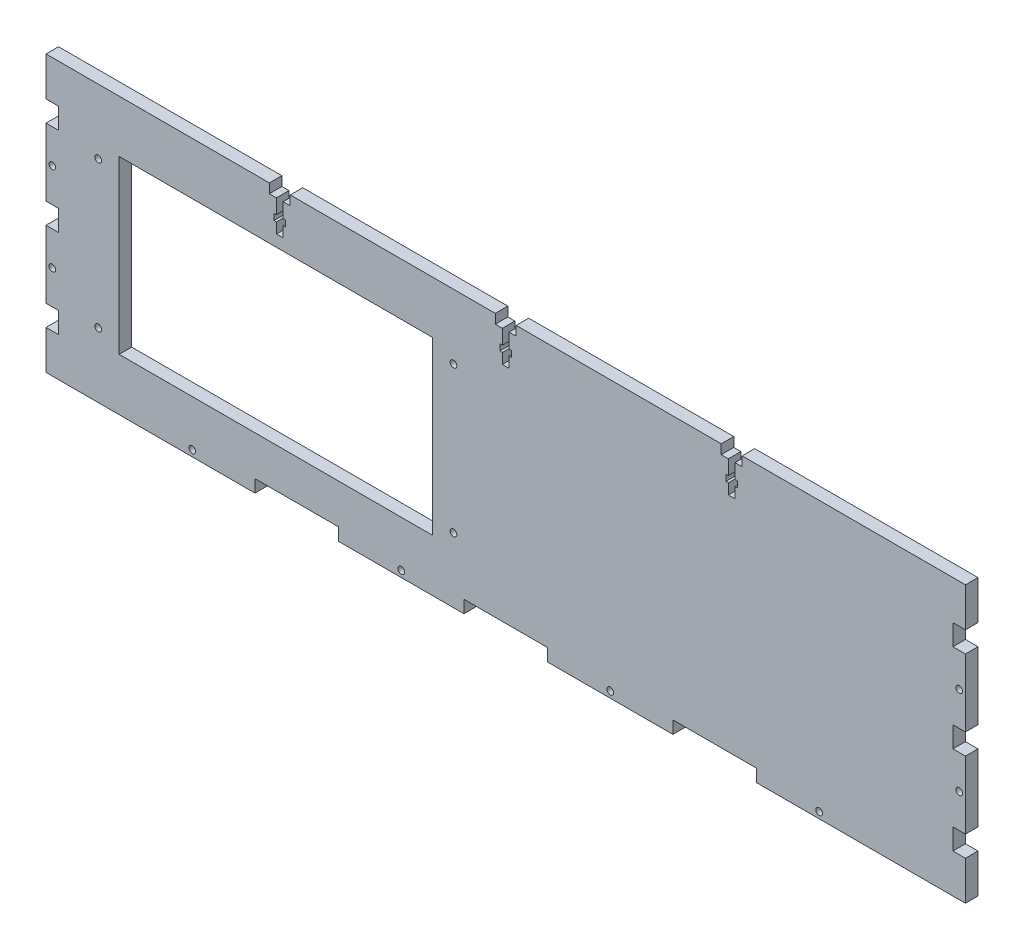
SolidWorks part; units mm, degrees
ref_plane "Front Plane" through (0, 0, 0) normal (0, 0, 1) x (1, 0, 0)
ref_plane "Top Plane" through (0, 0, 0) normal (0, 1, 0) x (1, 0, 0)
ref_plane "Right Plane" through (0, 0, 0) normal (1, 0, 0) x (0, 0, -1)
sketch "Sketch1" plane through (0, 0, 0) normal (0, 0, 1) x (1, 0, 0)
  line L1 (-220, -66) -> (220, -66)
  line L2 (-220, -66) -> (-220, 66)
  line L3 (-220, 66) -> (220, 66)
  line L4 (220, -66) -> (220, 66)
  line L5 (-220, -66) -> (220, 66) construction
  line L6 (-220, 66) -> (220, -66) construction
  point P0 (0, 0)
  dimension "D1" = 440
  dimension "D2" = 132
extrude "Boss-Extrude1" add sketch "Sketch1" along normal blind 6
sketch "Sketch2" plane through (0, 0, 0) normal (0, 0, -1) x (-1, 0, 0)
  line L0 (220, 47.3321) -> (220, 37.3321) construction
  line L1 (220, 37.3321) -> (214, 37.3321) construction
  line L2 (214, 37.3321) -> (214, 47.3321) construction
  line L3 (214, 47.3321) -> (220, 47.3321) construction
  line L12 (220, -37.3321) -> (220, -47.3321) construction
  line L13 (220, -47.3321) -> (214, -47.3321) construction
  line L14 (214, -47.3321) -> (214, -37.3321) construction
  line L15 (214, -37.3321) -> (220, -37.3321) construction
  line L16 (220, 47.3321) -> (220, 37.3321)
  line L17 (220, 37.3321) -> (214, 37.3321)
  line L18 (214, 37.3321) -> (214, 47.3321)
  line L19 (214, 47.3321) -> (220, 47.3321)
  line L20 (220, -37.3321) -> (220, -47.3321)
  line L21 (220, -47.3321) -> (214, -47.3321)
  line L22 (214, -47.3321) -> (214, -37.3321)
  line L23 (214, -37.3321) -> (220, -37.3321)
  line L24 (-214, -37.3321) -> (-214, -47.3321) construction
  line L25 (-214, -47.3321) -> (-220, -47.3321) construction
  line L26 (-220, -47.3321) -> (-220, -37.3321) construction
  line L27 (-220, -37.3321) -> (-214, -37.3321) construction
  line L28 (-214, 47.3321) -> (-214, 37.3321) construction
  line L29 (-214, 37.3321) -> (-220, 37.3321) construction
  line L30 (-220, 37.3321) -> (-220, 47.3321) construction
  line L31 (-220, 47.3321) -> (-214, 47.3321) construction
  line L32 (-214, -37.3321) -> (-214, -47.3321)
  line L33 (-214, -47.3321) -> (-220, -47.3321)
  line L34 (-220, -47.3321) -> (-220, -37.3321)
  line L35 (-220, -37.3321) -> (-214, -37.3321)
  line L36 (-214, 47.3321) -> (-214, 37.3321)
  line L37 (-214, 37.3321) -> (-220, 37.3321)
  line L38 (-220, 37.3321) -> (-220, 47.3321)
  line L39 (-220, 47.3321) -> (-214, 47.3321)
  line L44 (220, -5) -> (220, 5)
  line L45 (214, -5) -> (220, -5)
  line L46 (214, 5) -> (214, -5)
  line L47 (220, 5) -> (214, 5)
  line L48 (220, -5) -> (220, 5)
  line L49 (214, -5) -> (220, -5)
  line L50 (214, 5) -> (214, -5)
  line L51 (220, 5) -> (214, 5)
  line L52 (-214, -5) -> (-214, 5)
  line L53 (-220, -5) -> (-214, -5)
  line L54 (-220, 5) -> (-220, -5)
  line L55 (-214, 5) -> (-220, 5)
  line L56 (-214, -5) -> (-214, 5)
  line L57 (-220, -5) -> (-214, -5)
  line L58 (-220, 5) -> (-220, -5)
  line L59 (-214, 5) -> (-220, 5)
  circle A0 centre (217, 21.1661) radius 1.6 construction
  circle A1 centre (217, -21.1661) radius 1.6 construction
  circle A2 centre (-217, 21.1661) radius 1.6 construction
  circle A3 centre (-217, -21.1661) radius 1.6 construction
  circle A4 centre (217, 21.1661) radius 1.6
  circle A5 centre (217, -21.1661) radius 1.6
  circle A6 centre (-217, 21.1661) radius 1.6
  circle A7 centre (-217, -21.1661) radius 1.6
  dimension "D2" = 0
  dimension "D3" = 0
extrude "Cut-Extrude1" cut sketch "Sketch2" against normal up to next
sketch "Sketch3" plane through (0, 0, 0) normal (0, 0, -1) x (-1, 0, 0)
  circle A0 centre (-150, -63) radius 1.6 construction
  circle A1 centre (-50, -63) radius 1.6 construction
  circle A2 centre (50, -63) radius 1.6 construction
  circle A3 centre (150, -63) radius 1.6 construction
  circle A4 centre (-150, -63) radius 1.6
  circle A5 centre (-50, -63) radius 1.6
  circle A6 centre (50, -63) radius 1.6
  circle A7 centre (150, -63) radius 1.6
extrude "Cut-Extrude2" cut sketch "Sketch3" against normal up to next
sketch "Sketch4" plane through (0, 0, 0) normal (0, 0, -1) x (-1, 0, 0)
  line L0 (80, -66) -> (120, -66) construction
  line L1 (120, -66) -> (120, -60) construction
  line L2 (120, -60) -> (80, -60) construction
  line L3 (80, -60) -> (80, -66) construction
  line L4 (-20, -66) -> (20, -66) construction
  line L5 (20, -66) -> (20, -60) construction
  line L6 (20, -60) -> (-20, -60) construction
  line L7 (-20, -60) -> (-20, -66) construction
  line L8 (-120, -66) -> (-80, -66) construction
  line L9 (-80, -66) -> (-80, -60) construction
  line L10 (-80, -60) -> (-120, -60) construction
  line L11 (-120, -60) -> (-120, -66) construction
  line L12 (80, -66) -> (120, -66)
  line L13 (120, -66) -> (120, -60)
  line L14 (120, -60) -> (80, -60)
  line L15 (80, -60) -> (80, -66)
  line L16 (-20, -66) -> (20, -66)
  line L17 (20, -66) -> (20, -60)
  line L18 (20, -60) -> (-20, -60)
  line L19 (-20, -60) -> (-20, -66)
  line L20 (-120, -66) -> (-80, -66)
  line L21 (-80, -66) -> (-80, -60)
  line L22 (-80, -60) -> (-120, -60)
  line L23 (-120, -60) -> (-120, -66)
extrude "Cut-Extrude3" cut sketch "Sketch4" against normal up to next
sketch "Sketch5" plane through (0, 66, 0) normal (0, 1, 0) x (1, 0, 0)
  line L0 (220, 0) -> (-220, 0) construction
  line L1 (-113.125, -6) -> (-103.125, -6)
  line L2 (-113.125, -6) -> (-113.125, 0)
  line L3 (-113.125, 0) -> (-103.125, 0)
  line L4 (-103.125, -6) -> (-103.125, 0)
  line L5 (-113.125, -6) -> (-103.125, 0) construction
  line L6 (-113.125, 0) -> (-103.125, -6) construction
  line L7 (-103.125, -6) -> (-103.125, 0) construction
  line L8 (5, -6) -> (5, 0) construction
  line L9 (-5, -6) -> (5, -6)
  line L10 (-5, -6) -> (-5, 0)
  line L11 (-5, 0) -> (5, 0)
  line L12 (5, -6) -> (5, 0)
  line L13 (-5, -6) -> (5, 0) construction
  line L14 (-5, 0) -> (5, -6) construction
  line L15 (113.125, -6) -> (113.125, 0) construction
  line L16 (103.125, -6) -> (113.125, -6)
  line L17 (103.125, -6) -> (103.125, 0)
  line L18 (103.125, 0) -> (113.125, 0)
  line L19 (113.125, -6) -> (113.125, 0)
  line L20 (103.125, -6) -> (113.125, 0) construction
  line L21 (103.125, 0) -> (113.125, -6) construction
  point P0 (-108.125, -3)
  point P10 (0, -3)
  point P18 (108.125, -3)
extrude "Cut-Extrude4" cut sketch "Sketch5" against normal blind 4.5
sketch "Sketch6" plane through (0, 0, 0) normal (0, 0, -1) x (-1, 0, 0)
  line L0 (-108.125, 61.5) -> (-108.125, 46.5) construction
  line L1 (-113.125, 61.5) -> (-103.125, 61.5) construction
  line L2 (-109.725, 61.5) -> (-109.725, 54.5)
  line L3 (-106.525, 61.5) -> (-106.525, 54.5)
  line L4 (-109.725, 61.5) -> (-106.525, 61.5)
  line L5 (-109.725, 46.5) -> (-106.525, 46.5)
  line L6 (-106.525, 51.5) -> (-105.325, 51.5)
  line L7 (-110.925, 54.5) -> (-109.725, 54.5)
  line L8 (-110.925, 54.5) -> (-110.925, 51.5)
  line L9 (-110.925, 51.5) -> (-109.725, 51.5)
  line L10 (-105.325, 54.5) -> (-105.325, 51.5)
  line L11 (-110.925, 54.5) -> (-105.325, 51.5) construction
  line L12 (-110.925, 51.5) -> (-105.325, 54.5) construction
  line L13 (-106.525, 51.5) -> (-106.525, 46.5)
  line L14 (-106.525, 61.5) -> (-106.525, 46.5) construction
  line L15 (-109.725, 51.5) -> (-109.725, 46.5)
  line L16 (-109.725, 61.5) -> (-109.725, 46.5) construction
  line L17 (-106.525, 54.5) -> (-105.325, 54.5)
  line L18 (-1.595, 61.5) -> (-1.595, 54.5)
  line L19 (1.605, 61.5) -> (1.605, 54.5)
  line L20 (-1.595, 61.5) -> (1.605, 61.5)
  line L21 (-1.595, 46.5) -> (1.605, 46.5)
  line L22 (1.605, 51.5) -> (2.805, 51.5)
  line L23 (-2.795, 54.5) -> (-1.595, 54.5)
  line L24 (-2.795, 54.5) -> (-2.795, 51.5)
  line L25 (-2.795, 51.5) -> (-1.595, 51.5)
  line L26 (2.805, 54.5) -> (2.805, 51.5)
  line L27 (1.605, 51.5) -> (1.605, 46.5)
  line L28 (-1.595, 51.5) -> (-1.595, 46.5)
  line L29 (1.605, 54.5) -> (2.805, 54.5)
  line L30 (0.005, 61.5) -> (0.005, 46.5) construction
  line L31 (-2.795, 54.5) -> (2.805, 51.5) construction
  line L32 (-2.795, 51.5) -> (2.805, 54.5) construction
  line L33 (106.535, 61.5) -> (106.535, 54.5)
  line L34 (109.735, 61.5) -> (109.735, 54.5)
  line L35 (106.535, 61.5) -> (109.735, 61.5)
  line L36 (106.535, 46.5) -> (109.735, 46.5)
  line L37 (109.735, 51.5) -> (110.935, 51.5)
  line L38 (105.335, 54.5) -> (106.535, 54.5)
  line L39 (105.335, 54.5) -> (105.335, 51.5)
  line L40 (105.335, 51.5) -> (106.535, 51.5)
  line L41 (110.935, 54.5) -> (110.935, 51.5)
  line L42 (109.735, 51.5) -> (109.735, 46.5)
  line L43 (106.535, 51.5) -> (106.535, 46.5)
  line L44 (109.735, 54.5) -> (110.935, 54.5)
  line L45 (108.135, 61.5) -> (108.135, 46.5) construction
  line L46 (105.335, 54.5) -> (110.935, 51.5) construction
  line L47 (105.335, 51.5) -> (110.935, 54.5) construction
  point P8 (-108.125, 53)
  point P25 (0.005, 53)
  point P40 (108.135, 53)
  dimension "D1" = 15
  dimension "D4" = 5.6
  dimension "D5" = 3
  dimension "D6" = 7
  dimension "D2" = 1.6
  dimension "D3" = 1.6
  dimension "D7" = 3
extrude "Cut-Extrude5" cut sketch "Sketch6" against normal up to next
sketch "Sketch7" plane through (0, 0, 0) normal (0, 0, -1) x (-1, 0, 0)
  line L0 (0, 0) -> (220, 0) construction
  line L1 (220, 37.3321) -> (220, 5) construction
  line L2 (113.125, 66) -> (220, 66) construction
  line L3 (35, -41) -> (185, -41)
  line L4 (35, -41) -> (35, 41)
  line L5 (35, 41) -> (185, 41)
  line L6 (185, -41) -> (185, 41)
  line L7 (35, -41) -> (185, 41) construction
  line L8 (35, 41) -> (185, -41) construction
  line L9 (25, 35) -> (25, -35) construction
  line L10 (25, 35) -> (195, 35) construction
  line L11 (25, -35) -> (35, -35) construction
  line L12 (195, -35) -> (185, -35) construction
  circle A0 centre (25, 35) radius 1.6
  circle A1 centre (25, -35) radius 1.6
  circle A2 centre (195, 35) radius 1.6
  circle A3 centre (195, -35) radius 1.6
  point P3 (110, 0)
  point P4 (110, 0)
  point P15 (205, -34.5716)
  point P21 (110, 35)
  point P22 (25, 0)
  point P24 (15, -32.7571)
  point P27 (0, 0)
  point P28 (0, 0)
  dimension "D5" = 3.2
  dimension "D1" = 25
  dimension "D2" = 150
  dimension "D3" = 10
  dimension "D4" = 70
extrude "Cut-Extrude6" cut sketch "Sketch7" against normal through all
equation "\"m3_depth\"=15"
equation "\"D1@Sketch6\"=\"m3_depth\""
equation "\"m3_nut_width\"=5.6"
equation "\"D4@Sketch6\"=\"m3_nut_width\""
equation "\"m3_nut_thickness\"=3"
equation "\"D5@Sketch6\"=\"m3_nut_thickness\""
equation "\"m3_nut_depth\"=7"
equation "\"D6@Sketch6\"=\"m3_nut_depth\""
